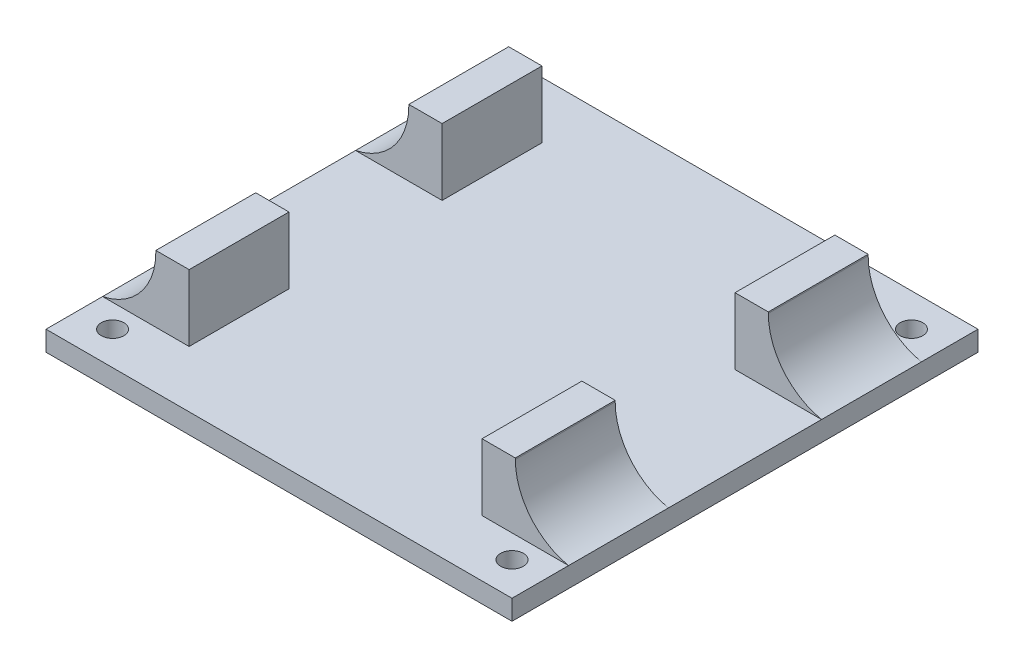
SolidWorks part; units mm, degrees
material "PLA"
ref_plane "Front Plane" through (0, 0, 0) normal (0, 0, 1) x (1, 0, 0)
ref_plane "Top Plane" through (0, 0, 0) normal (0, 1, 0) x (1, 0, 0)
ref_plane "Right Plane" through (0, 0, 0) normal (1, 0, 0) x (0, 0, -1)
sketch "Sketch1" plane through (0, 0, 0) normal (0, 1, 0) x (1, 0, 0)
  line L0 (35, 70) -> (35, 0) construction
  line L1 (0, 0) -> (70, 0)
  line L2 (0, 0) -> (0, 70)
  line L3 (0, 70) -> (70, 70)
  line L4 (70, 0) -> (70, 70)
  line L5 (0, 35) -> (70, 35) construction
  circle A0 centre (65, 65) radius 1.7
  circle A2 centre (5, 65) radius 1.7
  circle A3 centre (65, 5) radius 1.7
  circle A4 centre (5, 5) radius 1.7
  dimension "D5" = 3.4
  dimension "D1" = 70
  dimension "D2" = 70
  dimension "D3" = 5
  dimension "D4" = 5
extrude "Plate" add sketch "Sketch1" along normal blind 3
sketch "Sketch2" plane through (0, 3, 0) normal (0, 1, 0) x (1, 0, 0)
  line L0 (10.5, 54) -> (59.5, 54) construction
  line L1 (8, 61.5) -> (13, 61.5)
  line L2 (8, 61.5) -> (8, 46.5)
  line L3 (8, 46.5) -> (13, 46.5)
  line L4 (13, 61.5) -> (13, 46.5)
  line L5 (8, 61.5) -> (13, 46.5) construction
  line L6 (8, 46.5) -> (13, 61.5) construction
  line L7 (57, 61.5) -> (62, 61.5)
  line L8 (57, 61.5) -> (57, 46.5)
  line L9 (57, 46.5) -> (62, 46.5)
  line L10 (62, 61.5) -> (62, 46.5)
  line L11 (57, 61.5) -> (62, 46.5) construction
  line L12 (57, 46.5) -> (62, 61.5) construction
  line L13 (8, 23.5) -> (13, 23.5)
  line L14 (8, 23.5) -> (8, 8.5)
  line L15 (8, 8.5) -> (13, 8.5)
  line L16 (13, 23.5) -> (13, 8.5)
  line L17 (8, 23.5) -> (13, 8.5) construction
  line L18 (8, 8.5) -> (13, 23.5) construction
  line L19 (57, 23.5) -> (62, 23.5)
  line L20 (57, 23.5) -> (57, 8.5)
  line L21 (57, 8.5) -> (62, 8.5)
  line L22 (62, 23.5) -> (62, 8.5)
  line L23 (57, 23.5) -> (62, 8.5) construction
  line L24 (57, 8.5) -> (62, 23.5) construction
  line L25 (59.5, 54) -> (59.5, 16) construction
  line L26 (0, 70) -> (70, 70) construction
  line L27 (0, 70) -> (0, 0) construction
  point P0 (59.5, 54)
  point P9 (10.5, 16)
  point P14 (59.5, 16)
  point P27 (35, 54)
  point P29 (35, 70)
  point P30 (59.5, 35)
  point P31 (0, 35)
  dimension "D1" = 5
  dimension "D2" = 15
  dimension "D3" = 44
  dimension "D4" = 23
extrude "Boss-Extrude1" add sketch "Sketch2" along normal blind 10
fillet "Fillet1" radius 10 4 edges at (62, 3, -16) (62, 3, -54) (8, 3, -16) (8, 3, -54)
equation "\"WallSep\"= ( 70mm - 60 ) / 2"
equation "\"D4@Sketch1\"=\"WallSep\""
equation "\"D3@Sketch1\"=\"WallSep\""
